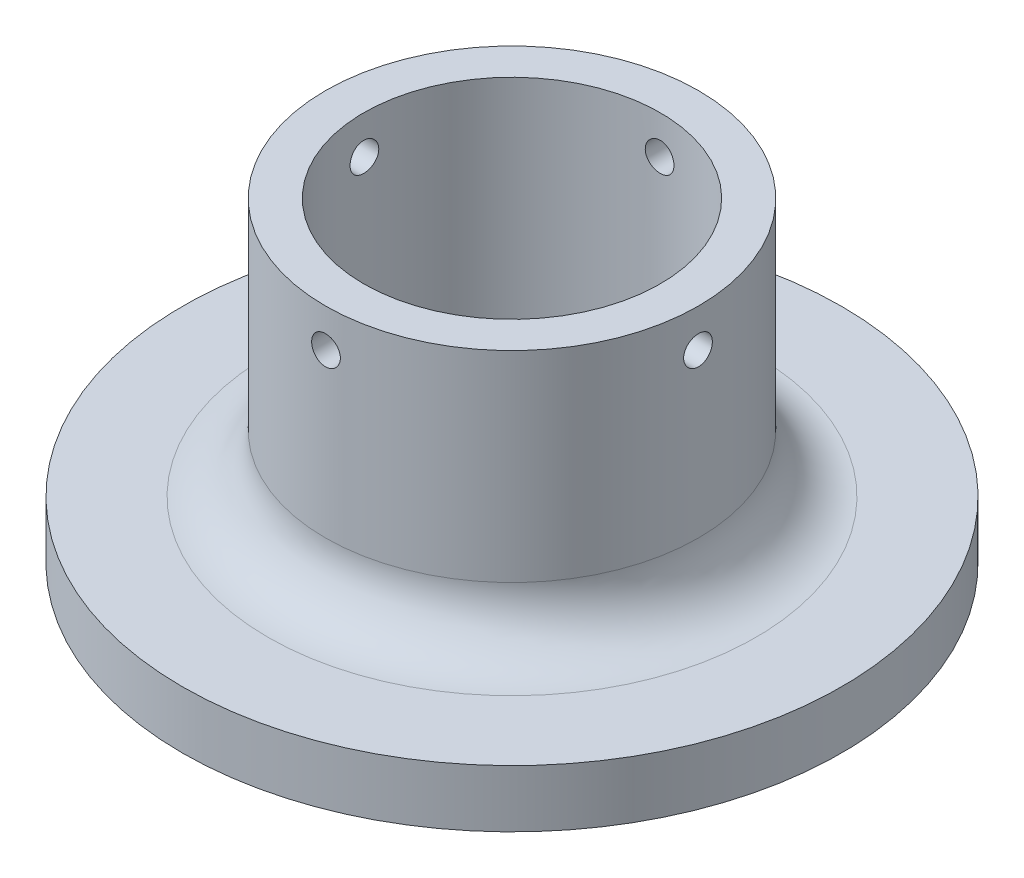
SolidWorks part; units mm, degrees
ref_plane "Alzado" through (0, 0, 0) normal (0, 0, 1) x (1, 0, 0)
ref_plane "Planta" through (0, 0, 0) normal (0, 1, 0) x (1, 0, 0)
ref_plane "Vista lateral" through (0, 0, 0) normal (1, 0, 0) x (0, 0, -1)
sketch "Croquis1" plane through (0, 0, 0) normal (0, 1, 0) x (1, 0, 0)
  line L0 (0, 7.1) -> (0, 0) construction
  line L16 (6.7525, 2.194) -> (0, 0) construction
  line L19 (4.1733, -5.744) -> (0, 0) construction
  line L22 (-4.1733, -5.744) -> (0, 0) construction
  line L25 (-6.7525, 2.194) -> (0, 0) construction
  circle A0 centre (0, 0) radius 17.225
  circle A16 centre (0, 0) radius 7.1
  point P31 (0, 0)
  point P33 (0, 0)
  point P35 (0, 0)
  dimension "D2" = 34.45
  dimension "D4" = 14.2
  dimension "D8" = 5
extrude "Saliente-Extruir1" add sketch "Croquis1" along normal blind 3
sketch "Croquis5" plane through (0, 0, 0) normal (0, -1, 0) x (1, 0, 0)
  circle A0 centre (0, 0) radius 7.1
  circle A1 centre (0, 0) radius 9.1
  dimension "D1" = 14.2
  dimension "D2" = 2
extrude "Saliente-Extruir2" add sketch "Croquis5" along normal blind 3
fillet "Redondeo1" radius 3 1 edges at (0, 0, 9.1)
sketch "Croquis10" plane through (0, 0, 0) normal (0, -1, 0) x (1, 0, 0)
  line L0 (0, 17.225) -> (0, -17.225) construction
  line L1 (4.2837, 16.6838) -> (-4.2837, -16.6838) construction
  line L2 (8.2982, 15.0944) -> (-8.2982, -15.0944) construction
  line L3 (11.7913, 12.5565) -> (-11.7913, -12.5565) construction
  line L4 (14.5435, 9.2296) -> (-14.5435, -9.2296) construction
  line L5 (16.3819, 5.3228) -> (-16.3819, -5.3228) construction
  line L6 (17.191, 1.0816) -> (-17.191, -1.0816) construction
  line L7 (16.9199, -3.2276) -> (-16.9199, 3.2276) construction
  line L8 (15.5856, -7.334) -> (-15.5856, 7.334) construction
  line L9 (13.2721, -10.9796) -> (-13.2721, 10.9796) construction
  line L10 (10.1246, -13.9353) -> (-10.1246, 13.9353) construction
  line L11 (6.3409, -16.0154) -> (-6.3409, 16.0154) construction
  line L12 (2.1589, -17.0892) -> (-2.1589, 17.0892) construction
  line L13 (-2.1589, -17.0892) -> (2.1589, 17.0892) construction
  line L14 (-6.3409, -16.0154) -> (6.3409, 16.0154) construction
  line L15 (-10.1246, -13.9353) -> (10.1246, 13.9353) construction
  line L16 (-13.2721, -10.9796) -> (13.2721, 10.9796) construction
  line L17 (-15.5856, -7.334) -> (15.5856, 7.334) construction
  line L18 (-16.9199, -3.2276) -> (16.9199, 3.2276) construction
  line L19 (-17.191, 1.0816) -> (17.191, -1.0816) construction
  line L20 (-16.3819, 5.3228) -> (16.3819, -5.3228) construction
  line L21 (-14.5435, 9.2296) -> (14.5435, -9.2296) construction
  line L22 (-11.7913, 12.5565) -> (11.7913, -12.5565) construction
  line L23 (-8.2982, 15.0944) -> (8.2982, -15.0944) construction
  line L24 (-4.2837, 16.6838) -> (4.2837, -16.6838) construction
  circle A0 centre (0, 0) radius 17.225 construction
  circle A1 centre (0, 15.276) radius 1.25
  circle A2 centre (3.799, 14.7961) radius 1.25
  circle A3 centre (7.3593, 13.3865) radius 1.25
  circle A4 centre (10.4572, 11.1357) radius 1.25
  circle A5 centre (12.898, 8.1853) radius 1.25
  circle A6 centre (14.5284, 4.7206) radius 1.25
  circle A7 centre (15.2459, 0.9592) radius 1.25
  circle A8 centre (15.0055, -2.8624) radius 1.25
  circle A9 centre (13.8222, -6.5042) radius 1.25
  circle A10 centre (11.7704, -9.7373) radius 1.25
  circle A11 centre (8.979, -12.3586) radius 1.25
  circle A12 centre (5.6235, -14.2033) radius 1.25
  circle A13 centre (1.9146, -15.1556) radius 1.25
  circle A14 centre (-1.9146, -15.1556) radius 1.25
  circle A15 centre (-5.6235, -14.2033) radius 1.25
  circle A16 centre (-8.979, -12.3586) radius 1.25
  circle A17 centre (-11.7704, -9.7373) radius 1.25
  circle A18 centre (-13.8222, -6.5042) radius 1.25
  circle A19 centre (-15.0055, -2.8624) radius 1.25
  circle A20 centre (-15.2459, 0.9592) radius 1.25
  circle A21 centre (-14.5284, 4.7206) radius 1.25
  circle A22 centre (-12.898, 8.1853) radius 1.25
  circle A23 centre (-10.4572, 11.1357) radius 1.25
  circle A24 centre (-7.3593, 13.3865) radius 1.25
  circle A25 centre (-3.799, 14.7961) radius 1.25
  point P107 (0, 0)
  dimension "D1" = 2.5
  dimension "D2" = 15.276
extrude "Cortar-Extruir1" cut sketch "Croquis10" against normal blind 1.1
sketch "Croquis12" plane through (0, 3, 0) normal (0, 1, 0) x (1, 0, 0)
  line L0 (0, 7.1) -> (0, -7.1) construction
  circle A1 centre (0, 0) radius 7.1 construction
  circle A2 centre (0, 0) radius 7.1
  circle A3 centre (0, 0) radius 7.75
  circle A4 centre (0, 0) radius 9.75
  dimension "D1" = 2
  dimension "D2" = 14.2
  dimension "D3" = 15.5
sketch "Croquis13" plane through (0, 3, 0) normal (0, 1, 0) x (1, 0, 0)
extrude "Saliente-Extruir3" add sketch "Croquis12" along normal blind 13.5 contours A4 A3 region at (-9.4742, 3, 0)
sketch "Croquis14" plane through (0, 0, 0) normal (1, 0, 0) x (0, 0, -1)
  line L0 (0, 16.5) -> (0, 3) construction
  line L1 (7.75, 16.5) -> (-7.75, 16.5) construction
  line L2 (17.225, 3) -> (-17.225, 3) construction
  line L3 (9.75, 16.5) -> (-9.75, 16.5) construction
  circle A0 centre (0, 14.5) radius 0.75
  dimension "D1" = 1.5
  dimension "D2" = 2
extrude "Cortar-Extruir3" cut sketch "Croquis14" against normal blind 12
pattern_circular "MatrizC1" count 4 every 90 about axis through (0, 16.5, 0) along (0, -1, 0) of "Cortar-Extruir3"
fillet "Redondeo2" radius 3 1 edges at (0, 3, 9.75)
